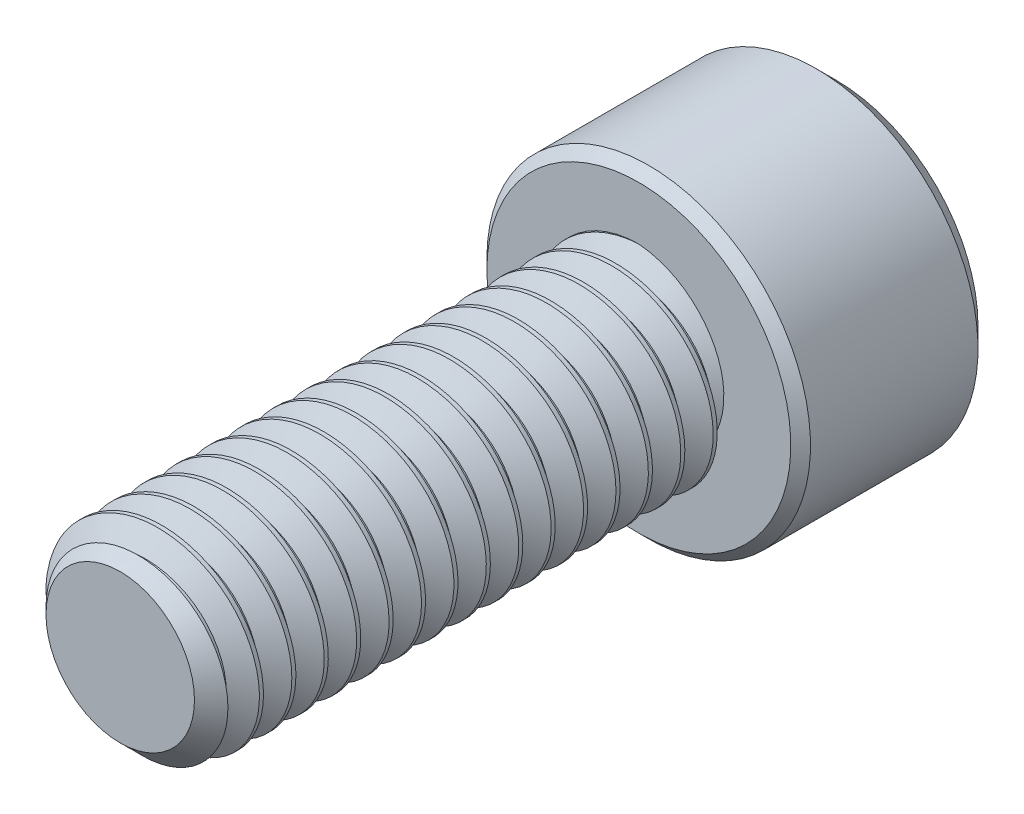
SolidWorks part; units mm, degrees
material "Plain Carbon Steel"
ref_plane "Front Plane" through (0, 0, 0) normal (0, 0, 1) x (1, 0, 0)
ref_plane "Top Plane" through (0, 0, 0) normal (0, 1, 0) x (1, 0, 0)
ref_plane "Right Plane" through (0, 0, 0) normal (1, 0, 0) x (0, 0, -1)
sketch "Sketch1" plane through (0, 0, 0) normal (0, 0, 1) x (1, 0, 0)
  line L0 (0, 2.413) -> (0, -2.413) construction
  circle A0 centre (0, 0) radius 2.413
  dimension "OD" = 4.826
extrude "Extrude1" add sketch "Sketch1" against normal blind 12.7
sketch "Sketch2" plane through (0, 0, 0) normal (0, 0, 1) x (1, 0, 0)
  circle A0 centre (0, 0) radius 2.413 construction
  circle A1 centre (0, 0) radius 2.413
curve "Helix/Spiral1" pitch 0.7937 height 13.4937 turns 17 parameters "pitch"=0.7937
chamfer "Chamfer3" distance 0.5953 angle 45 1 edges at (2.413, 0, 0)
sketch "Sketch3" plane through (0, 0, 0) normal (1, 0, 0) x (0, 0, -1)
  line L0 (-0.6945, 2.413) -> (-0.3969, 1.8974)
  line L1 (-0.3969, 1.8974) -> (-0.2977, 1.8974)
  line L2 (-0.2977, 1.8974) -> (0, 2.413)
  line L3 (-0.6945, 2.413) -> (0, 2.413)
  line L4 (-0.3473, 2.413) -> (-0.3473, 1.8974) construction
  line L5 (-0.5457, 2.1552) -> (-0.1488, 2.1552) construction
  line L6 (0, 2.413) -> (0, -2.413) construction
  dimension "D1" = 0.0992
  dimension "D2" = 0.3969
  dimension "D3" = 60
sweep "Cut-Sweep1" cut profiles "Sketch3" path "Helix/Spiral1"
sketch "Sketch6" plane through (0, 0, -12.7) normal (0, 0, -1) x (-1, 0, 0)
  circle A0 centre (0, 0) radius 3.9624
  dimension "head dia" = 7.9248
extrude "Extrude2" add sketch "Sketch6" along normal blind 4.826
sketch "Sketch7" plane through (0, 0, -17.526) normal (0, 0, -1) x (-1, 0, 0)
  line L1 (0, 2.2914) -> (-1.9844, 1.1457)
  line L2 (-1.9844, 1.1457) -> (-1.9844, -1.1457)
  line L3 (-1.9844, -1.1457) -> (0, -2.2914)
  line L4 (0, -2.2914) -> (1.9844, -1.1457)
  line L5 (1.9844, -1.1457) -> (1.9844, 1.1457)
  line L6 (1.9844, 1.1457) -> (0, 2.2914)
  circle A0 centre (0, 0) radius 1.9844 construction
  dimension "hex dia" = 3.9688
extrude "Cut-Extrude1" cut sketch "Sketch7" against normal blind 2.9766
sketch "Sketch8" plane through (0, 0, -17.526) normal (0, 0, -1) x (-1, 0, 0)
  circle A0 centre (0, 0) radius 2.2914
extrude "Cut-Extrude2" cut sketch "Sketch8" against normal blind 0.4826 draft 45
chamfer "Chamfer1" distance 0.4826 angle 45 1 edges at (-3.9624, 0, -17.526)
chamfer "Chamfer2" distance 0.2413 angle 45 1 edges at (-3.9624, 0, -12.7)
sketch "Sketch9" plane through (0, 0, 0) normal (1, 0, 0) x (0, 0, -1)
  line L0 (0, 2.413) -> (0, -2.413) construction
  line L1 (4.3656, 2.413) -> (4.3656, -2.413) construction
  line L2 (12.7, 3.9624) -> (12.7, -3.9624) construction
  line L3 (17.526, 3.9624) -> (17.526, -3.9624) construction
  line L4 (17.526, 0) -> (0, 0) construction
  dimension "D1" = 4.3656
  dimension "D2" = 4.826
  dimension "D3" = 7.9248
  dimension "D4" = 12.7
equation "\"D3@Helix/Spiral1\" = \"screw length@Extrude1\"+\"pitch@Helix/Spiral1\""
equation "\"D1@Sketch3\" = \"pitch@Helix/Spiral1\"*.125"
equation "\"D2@Sketch3\" = \"pitch@Helix/Spiral1\"*.5"
equation "\"D1@Cut-Extrude1\" = \"hex dia@Sketch7\"*.75"
equation "\"D1@Chamfer1\" = \"head depth@Extrude2\"/10"
equation "\"D1@Sketch9\" = \"pitch@Helix/Spiral1\"*5.5"
equation "\"D1@Chamfer2\" = \"D1@Chamfer1\"/2"
equation "\"D1@Cut-Extrude2\" = \"D1@Chamfer2\"*2"
equation "\"D1@Chamfer3\" = \"pitch@Helix/Spiral1\"*.750"
equation "\"D2@Sketch9\" = \"head depth@Extrude2\""
equation "\"D3@Sketch9\" = \"head dia@Sketch6\""
equation "\"D4@Sketch9\" = \"screw length@Extrude1\""
